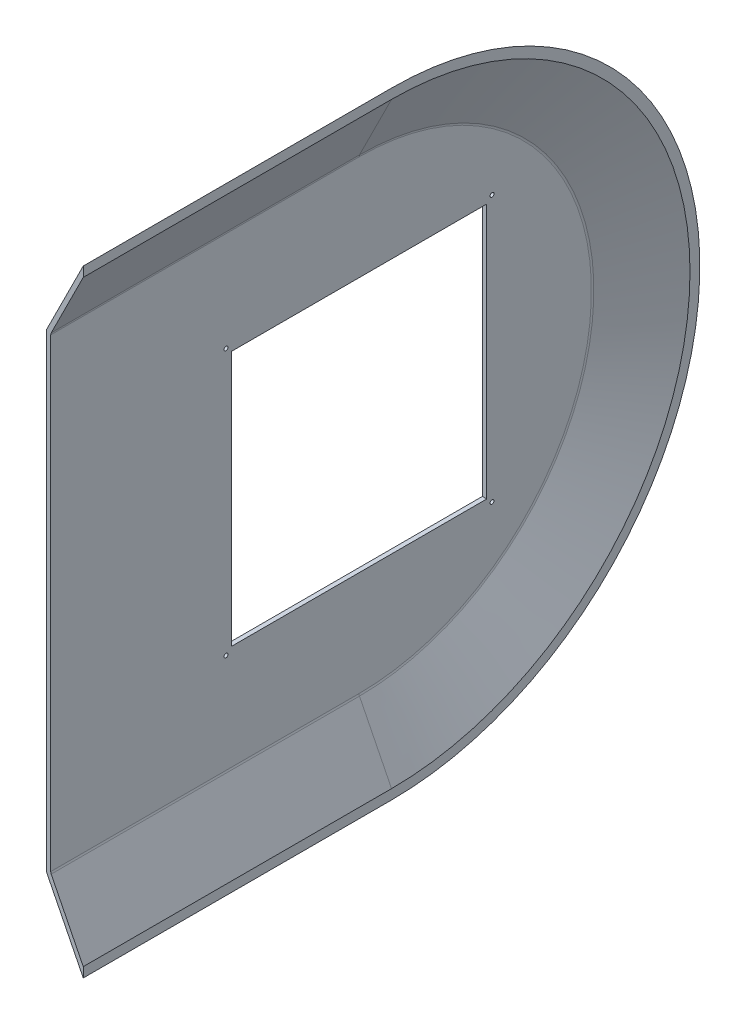
SolidWorks part; units mm, degrees
ref_plane "Plan de face" through (0, 0, 0) normal (0, 0, 1) x (1, 0, 0)
ref_plane "Plan de dessus" through (0, 0, 0) normal (0, 1, 0) x (1, 0, 0)
ref_plane "Plan de droite" through (0, 0, 0) normal (1, 0, 0) x (0, 0, -1)
sketch "Esquisse2" plane through (0, 0, 0) normal (0, 0, 1) x (1, 0, 0)
  line L0 (41.9268, 350) -> (41.9268, 0)
  line L5 (0, 266.1905) -> (41.9268, 350)
  line L6 (41.9268, 0) -> (0, 0)
  line L8 (0, 266.1905) -> (0, 0)
  dimension "D1" = 266.1905
  dimension "D2" = 350
  dimension "D3" = 153.423
  dimension "D4" = 90
revolve "Revolve1" add sketch "Esquisse2" angle 180 about L6
sketch "Sketch5" plane through (0, 0, 0) normal (0, 0, 1) x (1, 0, 0)
  line L3 (41.9268, 350) -> (0, 266.1905) construction
  line L4 (0, 266.1905) -> (41.9268, 350)
  line L5 (0, 266.1905) -> (0, -266.1905)
  line L6 (0, -266.1905) -> (41.9268, -350)
  line L7 (41.9268, -350) -> (41.9268, 350)
extrude "Boss-Extrude1" add sketch "Sketch5" along normal blind 350 contours L5 L6 L7 L4
shell "Shell2" thickness 5 removed face at (41.9268, 0, 87.5) removed face at (20.9634, 0, 350)
sketch "Sketch4" plane through (0, 0, 0) normal (-1, 0, 0) x (0, 0, 1)
  line L0 (0, -23.0597) -> (0, 23.0597) construction
  line L1 (-145, 145) -> (145, 145)
  line L2 (-145, 145) -> (-145, -145)
  line L3 (-145, -145) -> (145, -145)
  line L4 (145, 145) -> (145, -145)
  dimension "D1" = 290
  dimension "D2" = 290
  dimension "D3" = 145
  dimension "D4" = 145
extrude "Cut-Extrude1" cut sketch "Sketch4" against normal through all
sketch "Sketch7" plane through (0, 0, 0) normal (0, 0, 1) x (1, 0, 0)
  line L0 (0, 0) -> (75.7734, 0) construction
sketch "Sketch8" plane through (0, 0, 0) normal (-1, 0, 0) x (0, 0, 1)
  line L1 (-151, 151) -> (151, 151)
  line L2 (-151, 151) -> (-151, -151)
  line L3 (-151, -151) -> (151, -151)
  line L4 (151, 151) -> (151, -151)
  point P4 (0, 151)
  point P6 (151, 0)
  dimension "D1" = 302
  dimension "D2" = 302
  dimension "D3" = 0
  dimension "D4" = 0
hole_wizard "M4 Clearance Hole1" positions "Sketch11" profile "Sketch10" hole size "M4" standard "ANSI Metric"
sketch "Sketch11" plane through (0, 0, 0) normal (-1, 0, 0) x (0, 0, 1)
  point P2 (151, 151)
  point P5 (151, -151)
  point P8 (-151, -151)
  point P11 (-151, 151)
sketch "Sketch10" plane through (0, 151, 151) normal (0, 1, 0) x (0, 0, 1)
  line L0 (0, 0) -> (0, 31.3519)
  line L1 (0, 31.3519) -> (2.25, 30)
  line L2 (2.25, 30) -> (2.25, 0)
  line L5 (2.25, 0) -> (0, 0)
  line L10 (0, 31.3519) -> (-2.25, 30) construction
  line L11 (0, -6.35) -> (0, 107.95) construction
  dimension "Hole Dia." = 4.5
  dimension "Hole Depth" = 30
  dimension "Drill Angle" = 118
fillet "Fillet1" radius 5 6 edges at (5, -265.0097, 175) (5, 0, -265.0097) (5, 265.0097, 175) (0, -266.1905, 175) (0, 0, -266.1905) (0, 266.1905, 175)
equation "\"D3@Sketch4\"=\"D2@Sketch4\"/2"
equation "\"D4@Sketch4\"=\"D1@Sketch4\"/2"
